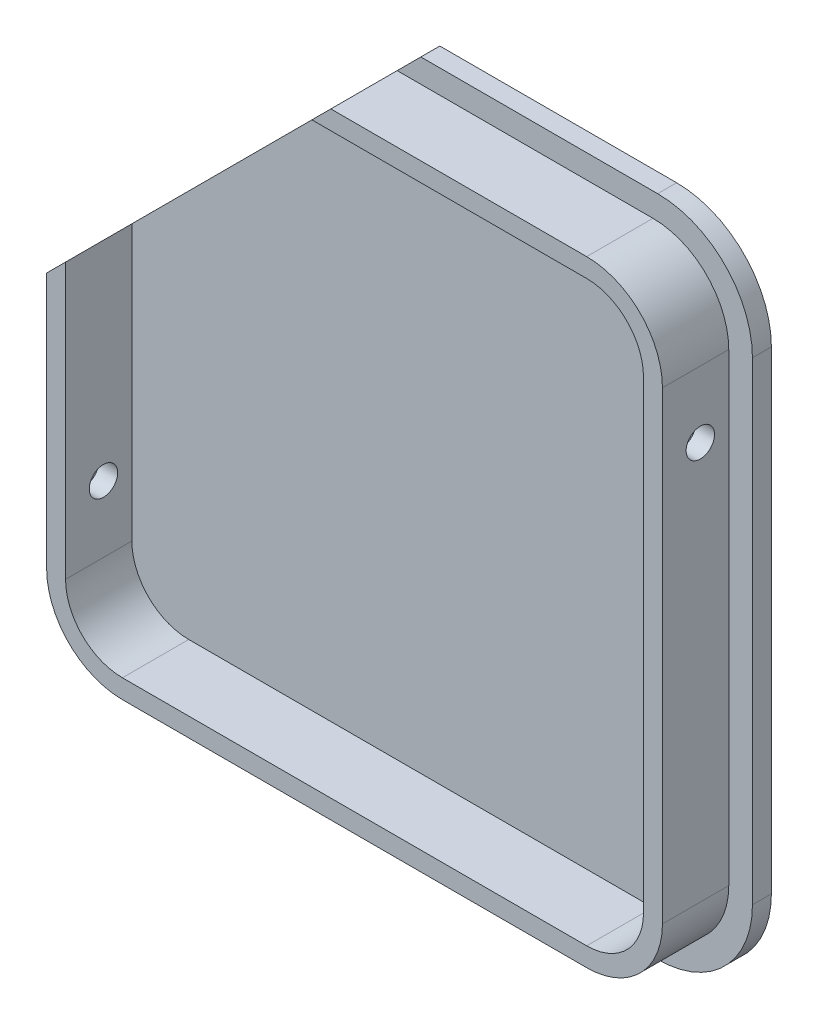
SolidWorks part; units mm, degrees
ref_plane "前视基准面" through (0, 0, 0) normal (0, 0, 1) x (1, 0, 0)
ref_plane "上视基准面" through (0, 0, 0) normal (0, 1, 0) x (1, 0, 0)
ref_plane "右视基准面" through (0, 0, 0) normal (1, 0, 0) x (0, 0, -1)
sketch "草图1" plane through (0, 0, 0) normal (0, 0, 1) x (1, 0, 0)
  line L1 (-23.1085, 22.918) -> (26.8915, 22.918)
  line L2 (-33.1085, 12.918) -> (-33.1085, -37.082)
  line L3 (-23.1085, -47.082) -> (26.8915, -47.082)
  line L4 (36.8915, 12.918) -> (36.8915, -37.082)
  arc A0 (-33.1085, 12.918) -> (-23.1085, 22.918) centre (-23.1085, 12.918) cw
  arc A1 (36.8915, 12.918) -> (26.8915, 22.918) centre (26.8915, 12.918) ccw
  arc A2 (26.8915, -47.082) -> (36.8915, -37.082) centre (26.8915, -37.082) ccw
  arc A3 (-23.1085, -47.082) -> (-33.1085, -37.082) centre (-23.1085, -37.082) cw
  point P6 (-33.1085, 22.918)
  point P9 (36.8915, 22.918)
  point P12 (36.8915, -47.082)
  dimension "D3" = 10
  dimension "D4" = 10
  dimension "D5" = 10
  dimension "D6" = 10
  dimension "D1" = 70
  dimension "D2" = 70
extrude "凸台-拉伸1" add sketch "草图1" along normal blind 2
sketch "草图2" plane through (0, 0, 2) normal (0, 0, 1) x (1, 0, 0)
  line L0 (26.8915, 22.918) -> (-23.1085, 22.918) construction
  line L1 (-22.6085, 20.418) -> (26.3915, 20.418)
  line L2 (-30.6085, 12.418) -> (-30.6085, -36.582)
  line L3 (-22.6085, -44.582) -> (26.3915, -44.582)
  line L4 (34.3915, 12.418) -> (34.3915, -36.582)
  line L5 (-33.1085, 12.918) -> (-33.1085, -37.082) construction
  line L6 (36.8915, -37.082) -> (36.8915, 12.918) construction
  line L7 (-23.1085, -47.082) -> (26.8915, -47.082) construction
  arc A0 (-30.6085, 12.418) -> (-22.6085, 20.418) centre (-22.6085, 12.418) cw
  arc A1 (34.3915, 12.418) -> (26.3915, 20.418) centre (26.3915, 12.418) ccw
  arc A2 (-22.6085, -44.582) -> (-30.6085, -36.582) centre (-22.6085, -36.582) cw
  arc A3 (26.3915, -44.582) -> (34.3915, -36.582) centre (26.3915, -36.582) ccw
  dimension "D5" = 8
  dimension "D6" = 8
  dimension "D7" = 8
  dimension "D8" = 8
  dimension "D1" = 2.5
  dimension "D2" = 2.5
  dimension "D3" = 2.5
  dimension "D4" = 2.5
extrude "凸台-拉伸2" add sketch "草图2" along normal blind 7
shell "抽壳1" thickness 2 removed face at (1.8915, -12.082, 9)
sketch "草图3" plane through (-30.6085, 0, 0) normal (-1, 0, 0) x (0, 0, 1)
  line L0 (2, 12.918) -> (2, -37.082) construction
  line L2 (9, -36.582) -> (2, -36.582) construction
  circle A0 centre (5, -29.582) radius 1.5
  dimension "D1" = 3
  dimension "D2" = 7
extrude "切除-拉伸1" cut sketch "草图3" against normal blind 7
sketch "草图4" plane through (34.3915, 0, 0) normal (1, 0, 0) x (0, 0, -1)
  line L0 (-2, -36.582) -> (-2, 12.418) construction
  line L1 (-9, 12.418) -> (-2, 12.418) construction
  circle A0 centre (-5, 5.418) radius 1.5
  dimension "D1" = 3
  dimension "D2" = 7
extrude "切除-拉伸2" cut sketch "草图4" against normal blind 7
sketch "草图5" plane through (0, 0, 2) normal (0, 0, 1) x (1, 0, 0)
  line L2 (-33.1085, 12.918) -> (-33.1085, -37.082) construction
  line L3 (26.8915, 22.918) -> (-23.1085, 22.918) construction
  line L6 (-33.1085, 12.918) -> (-33.1085, -12.082)
  line L7 (1.8915, 22.918) -> (-23.1085, 22.918)
  line L8 (1.8915, 22.918) -> (-33.1085, -12.082)
  arc A3 (-23.1085, 22.918) -> (-33.1085, 12.918) centre (-23.1085, 12.918) ccw construction
  arc A7 (-23.1085, 22.918) -> (-33.1085, 12.918) centre (-23.1085, 12.918) ccw
extrude "切除-拉伸3" cut sketch "草图5" against normal mid plane 20
